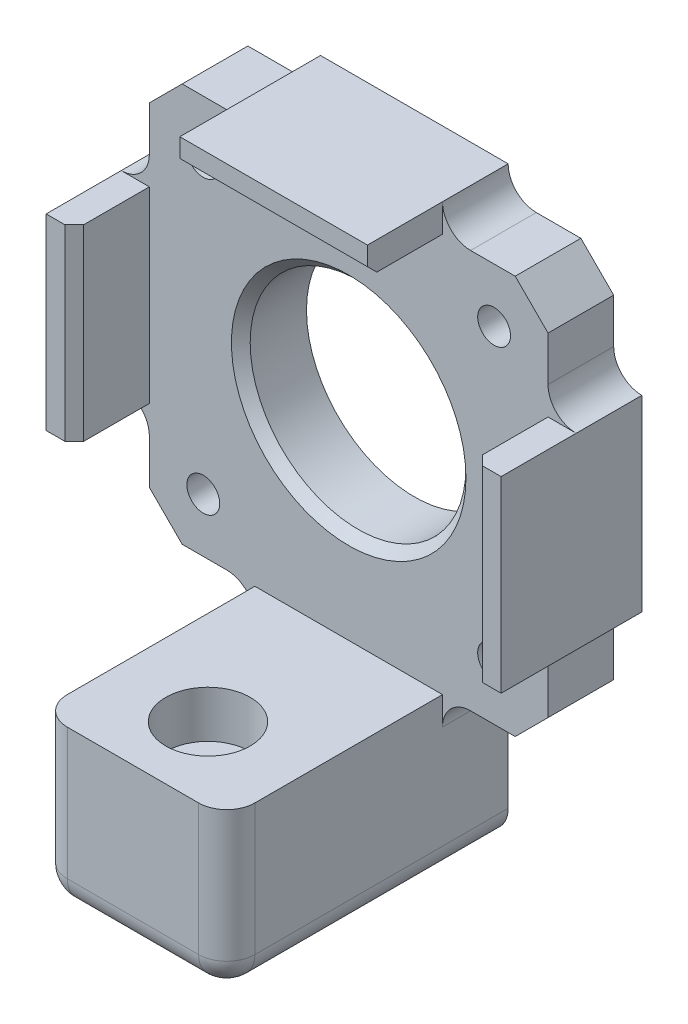
SolidWorks part; units mm, degrees
ref_plane "Plan de face" through (0, 0, 0) normal (0, 0, 1) x (1, 0, 0)
ref_plane "Plan de dessus" through (0, 0, 0) normal (0, 1, 0) x (1, 0, 0)
ref_plane "Plan de droite" through (0, 0, 0) normal (1, 0, 0) x (0, 0, -1)
sketch "Esquisse1" plane through (0, 0, 0) normal (0, 0, 1) x (1, 0, 0)
  line L0 (-17.75, 21.25) -> (-21.25, 17.75)
  line L1 (17.75, 21.25) -> (-17.75, 21.25)
  line L2 (21.25, 17.75) -> (21.25, -17.75)
  line L4 (-21.25, 17.75) -> (-21.25, -17.75)
  line L5 (21.25, 21.25) -> (-21.25, -21.25) construction
  line L6 (21.25, -21.25) -> (-21.25, 21.25) construction
  line L7 (21.25, 17.75) -> (17.75, 21.25)
  line L8 (-17.75, -21.25) -> (-21.25, -17.75)
  line L9 (21.25, -17.75) -> (17.75, -21.25)
  line L10 (-17.75, -21.25) -> (17.75, -21.25)
  line L13 (15.5, 15.5) -> (-15.5, 15.5) construction
  line L14 (15.5, 15.5) -> (15.5, -15.5) construction
  line L15 (15.5, -15.5) -> (-15.5, -15.5) construction
  line L16 (-15.5, 15.5) -> (-15.5, -15.5) construction
  line L17 (15.5, 15.5) -> (-15.5, -15.5) construction
  line L18 (15.5, -15.5) -> (-15.5, 15.5) construction
  line L19 (0, 37.3199) -> (0, -37.3199) construction
  line L20 (-53.6764, 0) -> (53.6764, 0) construction
  circle A0 centre (0, 0) radius 11.5
  circle A1 centre (-15.5, 15.5) radius 1.75
  circle A2 centre (15.5, 15.5) radius 1.75
  circle A3 centre (15.5, -15.5) radius 1.75
  circle A4 centre (-15.5, -15.5) radius 1.75
  point P0 (0, 0)
  point P24 (-21.25, 0)
  dimension "D3" = 23
  dimension "D4" = 3.5
  dimension "D2" = 42.5
  dimension "D5" = 42.5
  dimension "D10" = 21.25
  dimension "D18" = 31
  dimension "D19" = 31
extrude "Boss.-Extru.1" add sketch "Esquisse1" along normal blind 7
sketch "Esquisse2" plane through (0, 0, 0) normal (0, 0, -1) x (-1, 0, 0)
  line L0 (-17.75, 21.25) -> (17.75, 21.25) construction
  line L1 (-10, 21.25) -> (10, 21.25)
  line L2 (-10, 21.25) -> (-10, 24.25)
  line L3 (-10, 24.25) -> (10, 24.25)
  line L4 (10, 21.25) -> (10, 24.25)
  line L5 (24.25, 10) -> (24.25, -10)
  line L6 (21.25, -10) -> (24.25, -10)
  line L7 (21.25, 10) -> (24.25, 10)
  line L8 (21.25, 10) -> (21.25, -10)
  line L13 (-24.25, -10) -> (-24.25, 10)
  line L14 (-21.25, 10) -> (-24.25, 10)
  line L15 (-21.25, -10) -> (-24.25, -10)
  line L16 (-21.25, -10) -> (-21.25, 10)
  line L17 (10, -21.25) -> (-10, -21.25) [skipped]
  line L18 (10, -24.25) -> (-10, -24.25) [skipped]
  line L19 (10, -21.25) -> (10, -24.25) [skipped]
  line L20 (-10, -21.25) -> (-10, -24.25) [skipped]
  line L21 (-21.25, -17.75) -> (-21.25, 17.75) construction
  line L22 (21.25, 17.75) -> (21.25, -17.75) construction
  point P6 (0, 24.25)
  point P23 (0, 0)
  dimension "D1" = 20
  dimension "D2" = 3
  dimension "D3" = 4
extrude "Boss.-Extru.2" add sketch "Esquisse2" against normal blind 15
sketch "Esquisse3" plane through (0, 0, 0) normal (0, 0, -1) x (-1, 0, 0)
  line L1 (-10, -21.25) -> (10, -21.25)
  line L2 (-10, -21.25) -> (-10, -38.25)
  line L3 (-10, -38.25) -> (10, -38.25)
  line L4 (10, -21.25) -> (10, -38.25)
  line L5 (17.75, -21.25) -> (-17.75, -21.25) construction
  point P6 (0, -38.25)
  dimension "D1" = 20
  dimension "D2" = 17
extrude "Boss.-Extru.3" add sketch "Esquisse3" against normal blind 30
sketch "Esquisse4" plane through (0, -21.25, 0) normal (0, 1, 0) x (1, 0, 0)
  line L0 (-10, -30) -> (10, -30) construction
  circle A0 centre (0, -22) radius 2.5
  point P5 (0, -30)
  dimension "D1" = 5
  dimension "D2" = 8
extrude "Enlèv. mat.-Extru.1" cut sketch "Esquisse4" against normal through all
sketch "Esquisse5" plane through (0, -21.25, 0) normal (0, 1, 0) x (1, 0, 0)
  circle A0 centre (0, -22) radius 4.5
  circle A1 centre (0, -22) radius 2.5 construction
  dimension "D1" = 9
extrude "Enlèv. mat.-Extru.2" cut sketch "Esquisse5" against normal blind 5
sketch "Esquisse6" plane through (0, -38.25, 0) normal (0, -1, 0) x (-1, 0, 0)
  line L0 (3.0104, -19) -> (-3.0104, -19)
  arc A0 (-3.0104, -19) -> (3.0104, -19) centre (0, -22) ccw
  dimension "D1" = 8.5
  dimension "D2" = 3
extrude "Enlèv. mat.-Extru.3" cut sketch "Esquisse6" against normal blind 10
fillet "Congé1" radius 3 10 edges at (-21.25, -10, 3.5) (-21.25, 10, 3.5) (-10, 21.25, 3.5) (10, 21.25, 3.5) (21.25, 10, 3.5) (21.25, -10, 3.5) (-10, -38.25, 15) (10, -38.25, 15) (10, -21.25, 3.5) (-10, -21.25, 3.5)
fillet "Congé2" radius 3 5 edges at (10, -28.25, 30) (9.1213, -37.3713, 30) (0, -38.25, 30) (-9.1213, -37.3713, 30) (-10, -28.25, 30)
chamfer "Chanfrein1" distance 1 angle 45 4 edges at (11.5, 0, 7) (21.25, 0, 15) (0, 21.25, 15) (-21.25, 0, 15)
